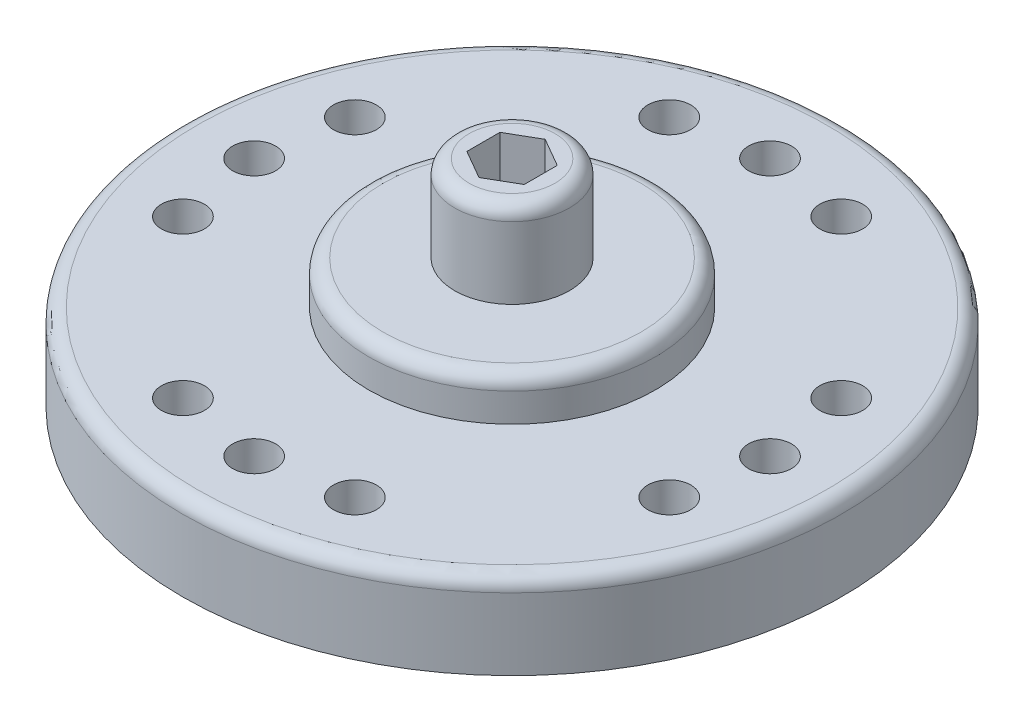
SolidWorks part; units mm, degrees
material "Comercialmente puro CP-Ti UNS R50400 (SS)"
ref_plane "Alzado" through (0, 0, 0) normal (0, 0, 1) x (1, 0, 0)
ref_plane "Planta" through (0, 0, 0) normal (0, 1, 0) x (1, 0, 0)
ref_plane "Vista lateral" through (0, 0, 0) normal (1, 0, 0) x (0, 0, -1)
sketch "Croquis1" plane through (0, 0, 0) normal (0, 1, 0) x (1, 0, 0)
  line L0 (-17.8, 0) -> (17.8, 0) construction
  line L1 (-17.8, -22.5) -> (17.8, -22.5) construction
  line L2 (17.8, -17.3) -> (17.8, 17.3)
  line L3 (11.8, 25.3) -> (-11.8, 25.3)
  line L4 (-17.8, -17.3) -> (-17.8, 17.3)
  line L5 (0, 25.3) -> (0, -25.3) construction
  line L6 (15, 25.3) -> (15, -22.1056) construction
  line L7 (-11.8, 25.3) -> (11.8, 25.3)
  line L8 (-12.2, 23.8) -> (-12.2, -18.2)
  line L9 (-10.7, -19.7) -> (10.7, -19.7)
  line L10 (12.2, 23.8) -> (12.2, -18.2)
  line L11 (12.2, 19.8) -> (17.8, 19.8)
  line L12 (17.4641, 18.4094) -> (13.4641, 24.4094)
  line L13 (1, 13.8774) -> (0, 14.4547)
  line L14 (0, 14.4547) -> (-1, 13.8774)
  line L15 (-1, 13.8774) -> (-1, 12.7226)
  line L16 (-1, 12.7226) -> (0, 12.1453)
  line L17 (0, 12.1453) -> (1, 12.7226)
  line L18 (1, 12.7226) -> (1, 13.8774)
  line L19 (-17.4641, 18.4094) -> (-13.4641, 24.4094)
  line L20 (17.4641, -18.4094) -> (13.4641, -24.4094)
  line L21 (-17.4641, -18.4094) -> (-13.4641, -24.4094)
  line L22 (-11.8, -25.3) -> (11.8, -25.3)
  line L23 (-10.7, 25.3) -> (10.7, 25.3)
  line L24 (12.2, 15.8) -> (17.8, 15.8)
  circle A0 centre (0, 13.3) radius 11.5
  circle A1 centre (0, 13.3) radius 2
  circle A2 centre (0, 13.3) radius 9 construction
  circle A3 centre (3, 21.7853) radius 0.75
  circle A4 centre (0, 13.3) radius 5
  circle A5 centre (0, 22.3) radius 0.75
  circle A6 centre (-3, 21.7853) radius 0.75
  circle A7 centre (15, 17.8) radius 1
  circle A8 centre (15, 0.8) radius 1
  circle A9 centre (15, -16.2) radius 1
  circle A10 centre (-8.5, -22.5) radius 1
  circle A11 centre (8.5, -22.5) radius 1
  circle A12 centre (-15, -16.2) radius 1
  circle A13 centre (-15, 0.8) radius 1
  circle A14 centre (-15, 17.8) radius 1
  circle A15 centre (0, 13.3) radius 1 construction
  arc A16 (13.4641, 24.4094) -> (11.8, 25.3) centre (11.8, 23.3) ccw
  arc A17 (17.4641, 18.4094) -> (17.8, 17.3) centre (15.8, 17.3) cw
  arc A18 (-17.4641, 18.4094) -> (-17.8, 17.3) centre (-15.8, 17.3) ccw
  arc A19 (-13.4641, 24.4094) -> (-11.8, 25.3) centre (-11.8, 23.3) cw
  arc A20 (13.4641, -24.4094) -> (11.8, -25.3) centre (11.8, -23.3) cw
  arc A21 (17.4641, -18.4094) -> (17.8, -17.3) centre (15.8, -17.3) ccw
  arc A22 (-13.4641, -24.4094) -> (-11.8, -25.3) centre (-11.8, -23.3) ccw
  arc A23 (-17.4641, -18.4094) -> (-17.8, -17.3) centre (-15.8, -17.3) cw
  arc A24 (10.7, -19.7) -> (12.2, -18.2) centre (10.7, -18.2) ccw
  arc A25 (-12.2, -18.2) -> (-10.7, -19.7) centre (-10.7, -18.2) ccw
  arc A26 (-12.2, 23.8) -> (-10.7, 25.3) centre (-10.7, 23.8) cw
  arc A27 (10.7, 25.3) -> (12.2, 23.8) centre (10.7, 23.8) cw
  point P1 (0, 25.3)
  point P4 (0, 25.3)
  point P56 (12.8704, 25.3)
  point P59 (17.8, 17.9056)
  dimension "D5" = 23
  dimension "D7" = 1.5
  dimension "D8" = 2
  dimension "D9" = 12.5
  dimension "D10" = 17
  dimension "D11" = 18
  dimension "D12" = 3
  dimension "D13" = 10
  dimension "D14" = 4
  dimension "D17" = 2
  dimension "D18" = 2
  dimension "D21" = 4
  dimension "D16" = 1.5
  dimension "D3" = 35.6
  dimension "D4" = 50.6
  dimension "D6" = 12
  dimension "D15" = 17
  dimension "D19" = 45
  dimension "D20" = 24.4
  dimension "D22" = 2
  dimension "D23" = 4
  dimension "D24" = 6
  dimension "D25" = 4.5
extrude "Saliente-Extruir1" add sketch "Croquis1" along normal blind 3 contours A0
extrude "Cortar-Extruir2" cut sketch "Croquis1<9>" along normal blind 3 contours A5 | A3 | A6 region at (3, 0, -21.7853) region at (0, 0, -22.3)
sketch "Croquis1<9>" plane through (0, 0, 0) normal (0, 1, 0) x (1, 0, 0) same geometry as "Croquis1"
pattern_circular "MatrizC2" count 4 over 360 about axis through (0, 3, -13.3) along (0, 1, 0) of "Cortar-Extruir2"
extrude "Saliente-Extruir2" add sketch "Croquis1<11>" along normal blind 1.5 from surface contours A4 starting at face at (9.2353, 3, -16.3)
sketch "Croquis1<11>" plane through (0, 0, 0) normal (0, 1, 0) x (1, 0, 0) same geometry as "Croquis1"
extrude "Saliente-Extruir3" add sketch "Croquis1<12>" along normal blind 3 from surface contours A1 L18 L17 L16 L15 L14 L13 region at (-1.9434, 0, -13.3) starting at face at (0, 4.5, -8.3)
sketch "Croquis1<12>" plane through (0, 0, 0) normal (0, 1, 0) x (1, 0, 0) same geometry as "Croquis1"
fillet "Redondeo1" radius 0.5 3 edges at (0, 7.5, -11.3) (0, 4.5, -8.3) (0, 3, -1.8)
extrude "Saliente-Extruir4" add sketch "Croquis1<13>" against normal blind 1 contours A4 A1 region at (-4.8586, 0, -13.3)
sketch "Croquis1<13>" plane through (0, 0, 0) normal (0, 1, 0) x (1, 0, 0) same geometry as "Croquis1"
